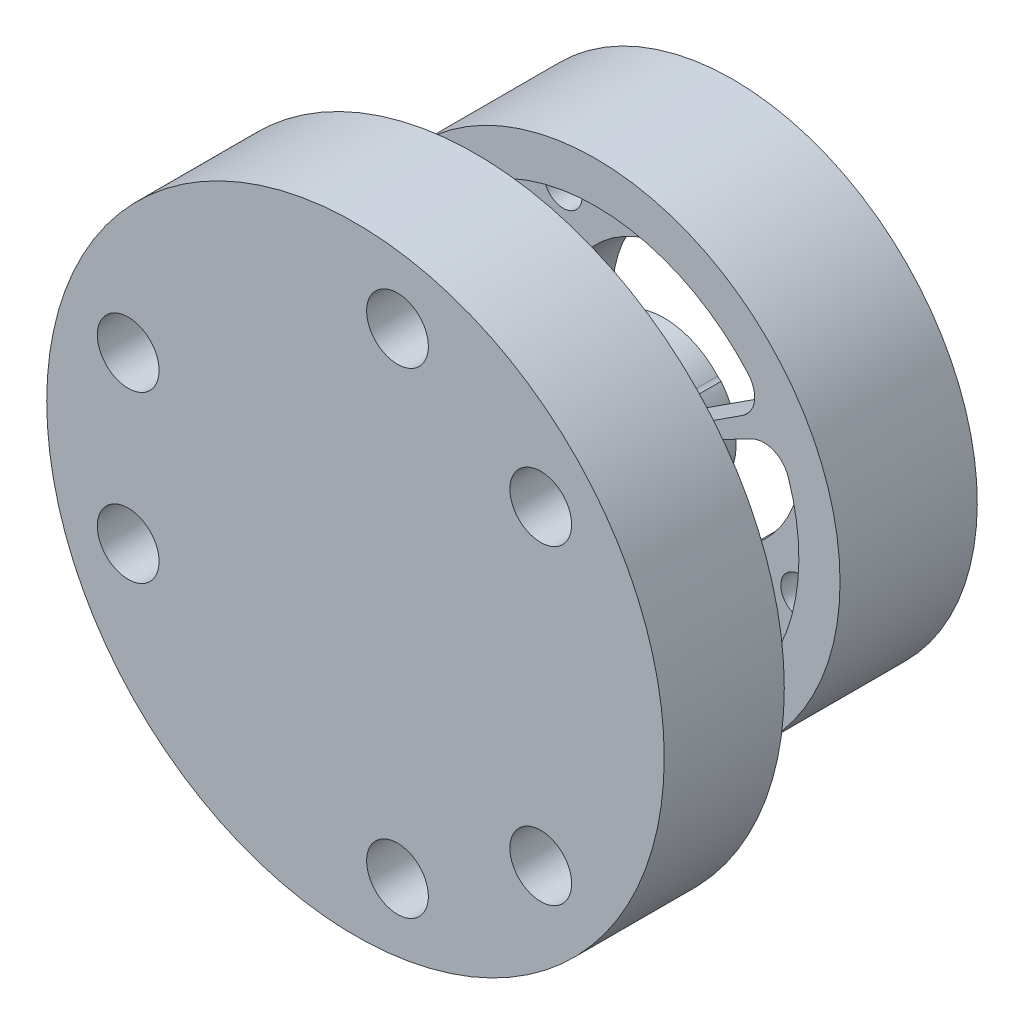
SolidWorks part; units mm, degrees
ref_plane "정면" through (0, 0, 0) normal (0, 0, 1) x (1, 0, 0)
ref_plane "윗면" through (0, 0, 0) normal (0, 1, 0) x (1, 0, 0)
ref_plane "우측면" through (0, 0, 0) normal (1, 0, 0) x (0, 0, -1)
sketch "스케치1" plane through (0, 0, 0) normal (0, 0, 1) x (1, 0, 0)
  line L0 (0, 0) -> (6.8943, 6.8943) construction
  line L1 (0, 0) -> (9.75, 0) construction
  line L2 (-4.25, -5.5621) -> (-4.25, -13.6015)
  line L3 (0, 0) -> (0, -14.25) construction
  line L4 (4.25, -5.5621) -> (4.25, -13.6015)
  arc A0 (4.25, -13.6015) -> (-4.25, -13.6015) centre (0, 0) ccw
  circle A1 centre (6.8943, 6.8943) radius 1.1
  circle A2 centre (0, 9.75) radius 2.1 construction
  circle A3 centre (0, 0) radius 9.75 construction
  arc A4 (4.25, -5.5621) -> (-4.25, -5.5621) centre (0, 0) ccw
  circle A5 centre (6.8943, -6.8943) radius 1.1
  circle A6 centre (-6.8943, -6.8943) radius 1.1
  circle A7 centre (-6.8943, 6.8943) radius 1.1
  point P19 (0, 0)
  dimension "D1" = 28.5
  dimension "D2" = 4.2
  dimension "D6" = 2.2
  dimension "D7" = 4.25
  dimension "D3" = 19.5
  dimension "D4" = 14
  dimension "D5" = 45
extrude "보스-돌출1" add sketch "스케치1" along normal blind 3
sketch "스케치2" plane through (0, 0, 3) normal (0, 0, 1) x (1, 0, 0)
  circle A0 centre (-6.8943, 6.8943) radius 2.1
  circle A1 centre (6.8943, 6.8943) radius 2.1
  circle A2 centre (6.8943, -6.8943) radius 2.1
  circle A3 centre (-6.8943, -6.8943) radius 2.1
  point P11 (0, 0)
  dimension "D2" = 4.2
  dimension "D1" = 4
extrude "컷-돌출1" [suppressed] cut sketch "스케치2" against normal blind 1.2
sketch "스케치3" plane through (0, 0, 3) normal (0, 0, 1) x (1, 0, 0)
  circle A0 centre (0, 0) radius 14.25
  circle A1 centre (0, 0) radius 11.85
  dimension "D1" = 28.5
  dimension "D2" = 23.7
extrude "보스-돌출2" add sketch "스케치3" along normal blind 1
sketch "스케치4" plane through (0, 0, 4) normal (0, 0, 1) x (1, 0, 0)
  line L0 (0, 0) -> (0, 14.25) construction
  line L1 (0, 0) -> (-9.9382, 6.454) construction
  line L2 (-8.5886, 5.5775) -> (-4.1393, 2.6881)
  line L3 (8.5886, 5.5775) -> (4.1393, 2.6881)
  line L4 (0.536, -10.2267) -> (0.2583, -4.9288)
  line L5 (9.1246, 4.6492) -> (4.3976, 2.2407)
  line L6 (-9.1246, 4.6492) -> (-4.3976, 2.2407)
  line L7 (-0.536, -10.2267) -> (-0.2583, -4.9288)
  circle A0 centre (0, 0) radius 14.25
  arc A2 (4.25, -11.0616) -> (-4.25, -11.0616) centre (0, 0) ccw construction
  arc A3 (-8.898, 7.8262) -> (8.898, 7.8262) centre (0, 0) cw
  arc A4 (-3.111, 2.8216) -> (3.111, 2.8216) centre (0, 0) cw
  arc A5 (11.2266, 3.7928) -> (2.3287, -11.6189) centre (0, 0) cw
  circle A9 centre (0, 0) radius 3.25 construction
  circle A10 centre (0, 0) radius 4 construction
  arc A11 (3.9991, 1.2834) -> (0.8881, -4.105) centre (0, 0) cw
  arc A12 (-2.3287, -11.6189) -> (-11.2266, 3.7928) centre (0, 0) cw
  arc A13 (-0.8881, -4.105) -> (-3.9991, 1.2834) centre (0, 0) cw
  arc A14 (8.5886, 5.5775) -> (8.898, 7.8262) centre (7.7716, 6.8355) ccw
  arc A15 (-8.5886, 5.5775) -> (-8.898, 7.8262) centre (-7.7716, 6.8355) cw
  arc A16 (-11.2266, 3.7928) -> (-9.1246, 4.6492) centre (-9.8055, 3.3127) cw
  arc A17 (-2.3287, -11.6189) -> (-0.536, -10.2267) centre (-2.0339, -10.1482) ccw
  arc A18 (2.3287, -11.6189) -> (0.536, -10.2267) centre (2.0339, -10.1482) cw
  arc A19 (11.2266, 3.7928) -> (9.1246, 4.6492) centre (9.8055, 3.3127) ccw
  arc A20 (-4.3976, 2.2407) -> (-3.9991, 1.2834) centre (-4.7608, 1.5279) cw
  arc A21 (-0.8881, -4.105) -> (-0.2583, -4.9288) centre (-1.0572, -4.887) cw
  arc A22 (0.2583, -4.9288) -> (0.8881, -4.105) centre (1.0572, -4.887) cw
  arc A23 (3.9991, 1.2834) -> (4.3976, 2.2407) centre (4.7608, 1.5279) cw
  arc A24 (4.1393, 2.6881) -> (3.111, 2.8216) centre (3.7036, 3.359) cw
  arc A25 (-3.111, 2.8216) -> (-4.1393, 2.6881) centre (-3.7036, 3.359) cw
  point P14 (9.9382, 6.454)
  point P24 (0, 0)
  point P32 (0, 0)
  point P47 (0, 0)
  point P48 (3.5224, 2.2875)
  point P51 (-3.5224, 2.2875)
  point P78 (0, 0)
  dimension "D2" = 28.5
  dimension "D3" = 6.5
  dimension "D4" = 8
  dimension "D5" = 57
  dimension "D7" = 1.5
  dimension "D8" = 1.5
  dimension "D9" = 0.8
  dimension "D1" = 4.2
  dimension "D6" = 3
extrude "보스-돌출3" add sketch "스케치4" along normal blind 4
sketch "스케치5" plane through (0, 0, 4) normal (0, 0, -1) x (-1, 0, 0)
  circle A0 centre (0, 0) radius 3.25
  dimension "D1" = 6.5
extrude "컷-돌출2" cut sketch "스케치5" against normal blind 2.5
sketch "스케치6" plane through (0, 0, 8) normal (0, 0, 1) x (1, 0, 0)
  circle A0 centre (0, 0) radius 3.5
  dimension "D1" = 7
extrude "보스-돌출4" add sketch "스케치6" along normal blind 7
sketch "스케치10" plane through (0, 0, 4) normal (0, 0, -1) x (-1, 0, 0)
  circle A0 centre (0, 0) radius 4.25
  circle A1 centre (0, 0) radius 11.85
extrude "컷-돌출3" cut sketch "스케치10" against normal blind 2
sketch "스케치7" plane through (0, 0, 15) normal (0, 0, 1) x (1, 0, 0)
  line L0 (0, 0) -> (-14.1, 0) construction
  line L1 (0, 0) -> (-13.2497, 4.8225) construction
  circle A0 centre (0, 0) radius 14.1 construction
  circle A1 centre (-13.2497, 4.8225) radius 1.6
  circle A2 centre (0, 0) radius 18
  circle A3 centre (-13.2497, -4.8225) radius 1.6
  circle A4 centre (10.8012, 9.0633) radius 1.6
  circle A5 centre (2.4484, 13.8858) radius 1.6
  circle A6 centre (2.4484, -13.8858) radius 1.6
  circle A7 centre (10.8012, -9.0633) radius 1.6
  point P20 (0, 0)
  dimension "D1" = 28.2
  dimension "D3" = 3.2
  dimension "D4" = 36
  dimension "D2" = 20
extrude "보스-돌출5" add sketch "스케치7" along normal blind 7
sketch "스케치8" plane through (0, 0, 15) normal (0, 0, -1) x (-1, 0, 0)
  circle A0 centre (13.2497, 4.8225) radius 2.75
  circle A1 centre (13.2497, -4.8225) radius 2.75
  circle A2 centre (-2.4484, -13.8858) radius 2.75
  circle A3 centre (-10.8012, -9.0633) radius 2.75
  circle A4 centre (-10.8012, 9.0633) radius 2.75
  circle A5 centre (-2.4484, 13.8858) radius 2.75
  point P17 (0, 0)
  dimension "D1" = 5.5
  dimension "D2" = 5.5
hole_wizard "M3 접시 머리 나사용 카운터싱크1" positions "3D스케치1" profile "스케치9" countersink size "M3" standard "ISO" end condition through all
sketch3d "3D스케치1"
  point P0 (2.4484, 13.8858, 15)
  point P3 (-13.2497, 4.8225, 15)
  point P6 (-13.2497, -4.8225, 15)
  point P9 (2.4484, -13.8858, 15)
  point P12 (10.8012, -9.0633, 15)
  point P15 (10.8012, 9.0633, 15)
sketch "스케치9" plane through (2.4484, 13.8858, 15) normal (1, 0, 0) x (0, 1, 0)
  line L0 (0, 0) -> (0, 7)
  line L1 (0, 7) -> (1.8, 7)
  line L2 (1.8, 7) -> (1.8, 1.35)
  line L3 (1.8, 1.35) -> (3.15, 0)
  line L5 (3.15, 0) -> (0, 0)
  line L6 (-1.8, 1.35) -> (-3.15, 0) construction
  line L11 (0, -6.35) -> (0, 107.95) construction
  dimension "관통 구멍 지름" = 3.6
  dimension "관통 구멍 깊이" = 7
  dimension "표면 카운터싱크 지름" = 6.3
  dimension "표면 카운터싱크 각도" = 90
ref_axis "기준축1" through (0, 0, 22) along (0, 0, -1)
